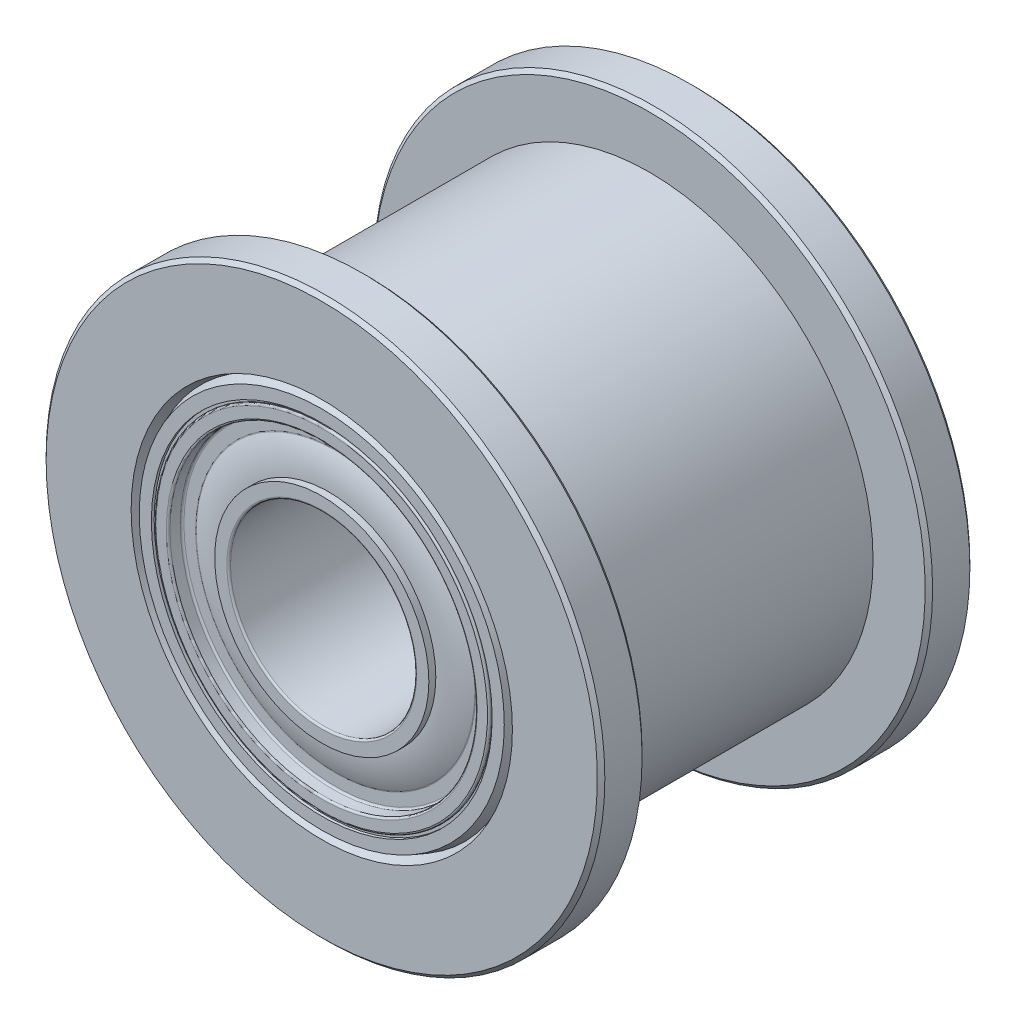
SolidWorks part; units mm, degrees
ref_plane "Front" through (0, 0, 0) normal (0, 0, 1) x (1, 0, 0)
ref_plane "Top" through (0, 0, 0) normal (0, 1, 0) x (1, 0, 0)
ref_plane "Right" through (0, 0, 0) normal (1, 0, 0) x (0, 0, -1)
sketch "Sketch1" plane through (0, 0, 0) normal (1, 0, 0) x (0, 0, -1)
  line L0 (-5, 0) -> (5, 0) construction
  line L1 (5, 7.5) -> (5, -7.5) construction
  line L2 (5, 7.5) -> (3.8, 7.5) construction
  line L3 (5, 2.5) -> (5, -2.5) construction
  line L4 (5, 6) -> (5, -6) construction
  line L5 (3, 0) -> (-3, 0) construction
  line L6 (3.8, 7.5) -> (3.8, 6) construction
  dimension "D3" = 1.2
  dimension "Width" = 10
  dimension "OD" = 15
  dimension "ID" = 5
  dimension "Diameter" = 12
  dimension "Max Belt Width" = 6
  dimension "Groove Depth" = 1.5
sketch "Sketch2" plane through (0, 0, 0) normal (1, 0, 0) x (0, 0, -1)
  line L0 (5, 2.5) -> (0, 2.5)
  line L1 (5, 2.5) -> (5, 2.875)
  line L2 (5, 7.5) -> (5, -7.5) construction
  line L3 (5, 2.875) -> (4.625, 2.875) construction
  line L4 (4.8125, 4.125) -> (4.8125, 2.875) construction
  line L5 (5, 4.5) -> (0, 4.5)
  line L6 (4.625, 3.75) -> (4.625, 4.125)
  line L7 (5, 4.5) -> (5, 4.125)
  line L8 (5, 4.125) -> (4.625, 4.125)
  line L9 (4.625, 4.125) -> (4.625, 2.875) construction
  line L10 (0, 4.5) -> (0, 2.5)
  line L11 (4.8125, 2.875) -> (5, 2.875)
  arc A0 (4.625, 3.75) -> (4.8125, 2.875) centre (2.6771, 2.875) cw
  dimension "D1" = 1.5
  dimension "D2" = 0.375
revolve "Revolve1" add sketch "Sketch2" angle 360 about L0
mirror "Mirror1" about plane through (0, 0, 0) normal (0, 0, 1) of bodies 108
sketch "Sketch3" plane through (0, 0, 0) normal (1, 0, 0) x (0, 0, -1)
  line L0 (3.8, 7.5) -> (5, 7.5)
  line L1 (5, 7.5) -> (5, 5.1184)
  line L2 (5, 7.5) -> (5, -7.5) construction
  line L3 (5, 5.1184) -> (4.7, 5.0092)
  line L4 (4.7, 5.0092) -> (5, 4.9)
  line L5 (5, 4.9) -> (5, 4.575)
  line L6 (4.925, 4.5) -> (4.925, 4.575)
  line L7 (5, 4.5) -> (-5, 4.5) construction
  line L8 (4.925, 4.575) -> (5, 4.575)
  line L9 (3.8, 7.5) -> (3.8, 6)
  line L10 (3.8, 6) -> (-3.8, 6)
  line L11 (0, 6) -> (0, 4.5) construction
  line L12 (-4.925, 4.5) -> (4.925, 4.5)
  line L13 (-3.8, 7.5) -> (-3.8, 6)
  line L14 (-4.925, 4.575) -> (-5, 4.575)
  line L15 (-4.925, 4.5) -> (-4.925, 4.575)
  line L16 (-5, 4.9) -> (-5, 4.575)
  line L17 (-4.7, 5.0092) -> (-5, 4.9)
  line L18 (-5, 5.1184) -> (-4.7, 5.0092)
  line L19 (-5, 7.5) -> (-5, 5.1184)
  line L20 (-3.8, 7.5) -> (-5, 7.5)
  line L21 (4.7, 5.0092) -> (5, 5.0092) construction
  line L22 (4.85, 5.0092) -> (4.85, 4.5) construction
  dimension "D1" = 40
  dimension "D2" = 0.3
  dimension "D3" = 0.075
  dimension "D4" = 0.4
revolve "Revolve2" add sketch "Sketch3" angle 360 about L0
sketch "Sketch4" plane through (0, 0, 0) normal (0, 0, 1) x (1, 0, 0)
  line L0 (-0.6, 6) -> (0.6, 6)
  line L1 (-0.6, 6) -> (-0.6, 5.4) construction
  line L2 (-0.6, 5.4) -> (0.6, 5.4) construction
  line L3 (0.6, 5.4) -> (0.6, 6) construction
  line L4 (0, 6) -> (0, 5.4) construction
  arc A0 (0.6, 6) -> (-0.6, 6) centre (0, 6) cw
  dimension "D1" = 0.6
  dimension "D3" = 1.2
extrude "Cut-Extrude1" [suppressed] cut sketch "Sketch4" against normal up to surface and the other way up to surface up to face at (6, 0, -3.8) other way up to face at (7.5, 0, 3.8)
fillet "Fillet1" [suppressed] radius 0.05
pattern_circular "CirPattern3" [suppressed] count 20 over 360 of bodies 114
chamfer "Chamfer1" distance 0.1 angle 45 4 edges at (7.5, 0, -5) (7.5, 0, -3.8) (7.5, 0, 3.8) (7.5, 0, 5)
fillet "Fillet2" radius 0.05 10 edges at (3.75, 0, 4.625) (4.125, 0, 4.625) (4.5, 0, 5) (4.125, 0, 5) (2.5, 0, 5) (2.5, 0, -5) (4.5, 0, -5) (3.75, 0, -4.625) (4.125, 0, -5) (2.875, 0, -5)
combine bodies "Combine1" operation type add bodies to combine 110 109
ref_axis "Center Axis 1" through (0, 0, -4.95) along (0, 0, 1)
ref_plane "Contact Plane 1" through (0, 0, -3) normal (0, 0, 1) x (1, 0, 0)
ref_plane "Contact Plane 2" through (0, 0, 3) normal (0, 0, 1) x (1, 0, 0)
equation "\"D1@Sketch4\"=\"Groove Depth@Sketch1\"/2.5"
equation "\"D3@Sketch4\"=\"Diameter@Sketch1\"/10"
equation "\"D2@Sketch3\"=\"D3@Sketch1\"/4"
equation "\"D1@Sketch2\"=(\"OD@Sketch1\"-\"Diameter@Sketch1\")/2"
equation "\"D2@Sketch2\"=\"D1@Sketch2\"/4"
equation "\"D3@Sketch3\"=\"D2@Sketch3\"/4"
equation "\"D4@Sketch3\"=\"D3@Sketch1\"/3"
